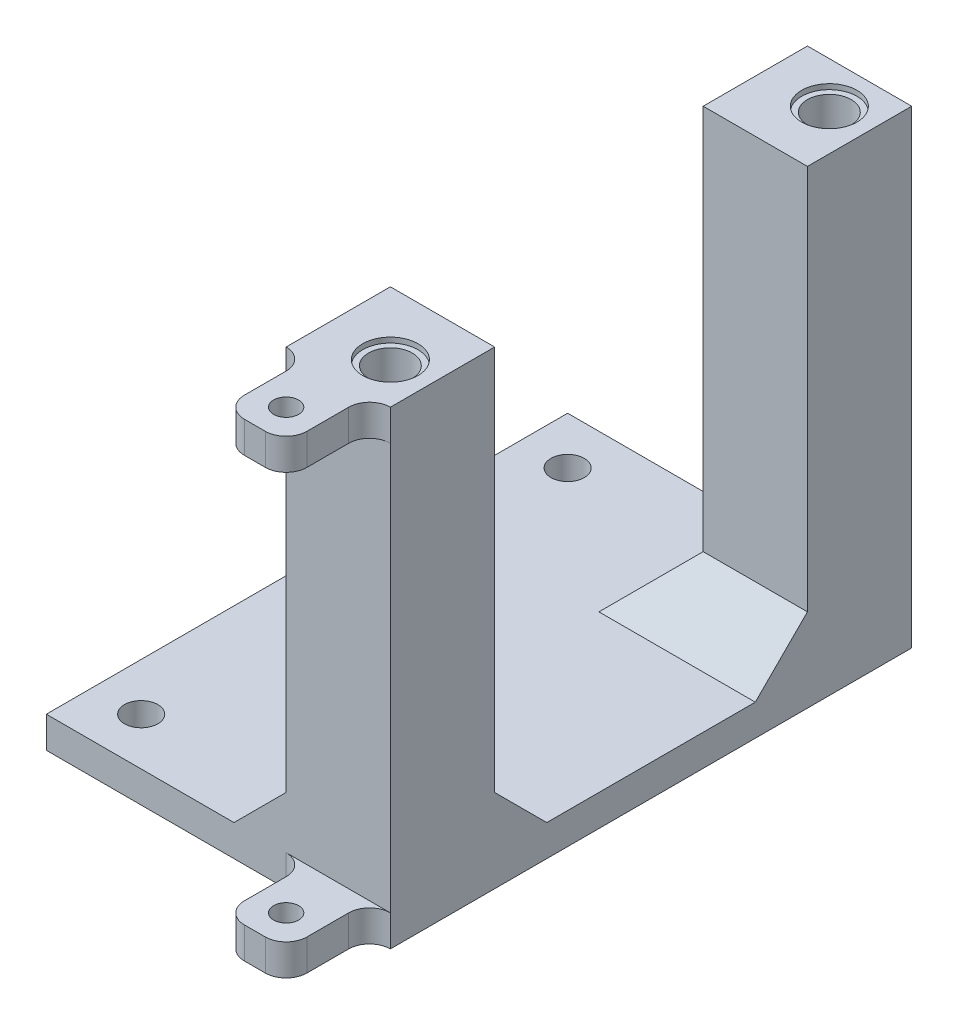
SolidWorks part; units mm, degrees
ref_plane "Front Plane" through (0, 0, 0) normal (0, 0, 1) x (1, 0, 0)
ref_plane "Top Plane" through (0, 0, 0) normal (0, 1, 0) x (1, 0, 0)
ref_plane "Right Plane" through (0, 0, 0) normal (1, 0, 0) x (0, 0, -1)
sketch "Sketch1" plane through (0, 0, 0) normal (0, 1, 0) x (1, 0, 0)
  line L1 (-6.5124, 9.686) -> (1.4876, 9.686)
  line L2 (-6.5124, 9.686) -> (-6.5124, -40.314)
  line L3 (-6.5124, -40.314) -> (1.4876, -40.314)
  line L4 (1.4876, 9.686) -> (1.4876, -40.314)
  line L5 (1.4876, 9.686) -> (26.4876, 9.686)
  line L6 (1.4876, 9.686) -> (1.4876, -40.314)
  line L7 (1.4876, -40.314) -> (26.4876, -40.314)
  line L8 (26.4876, 9.686) -> (26.4876, -40.314)
  circle A0 centre (-1.9624, -35.764) radius 1.6
  circle A1 centre (-1.9624, 5.136) radius 1.6
  dimension "D4" = 3.2
  dimension "D5" = 3.2
  dimension "D6" = 4.55
  dimension "D7" = 4.55
  dimension "D8" = 4.55
  dimension "D9" = 4.55
  dimension "D1" = 8
  dimension "D2" = 50
  dimension "D3" = 25
extrude "Boss-Extrude1" add sketch "Sketch1" along normal blind 3 contours A1 | A0 | L5 L8 L7 L3 L2 L1
sketch "Sketch2" plane through (0, 3, 0) normal (0, 1, 0) x (1, 0, 0)
  line L1 (26.4876, -40.314) -> (16.4876, -40.314)
  line L2 (26.4876, -40.314) -> (26.4876, -30.314)
  line L3 (26.4876, -30.314) -> (16.4876, -30.314)
  line L4 (16.4876, -40.314) -> (16.4876, -30.314)
  line L5 (26.4876, 9.686) -> (16.4876, 9.686)
  line L6 (26.4876, 9.686) -> (26.4876, -0.314)
  line L7 (26.4876, -0.314) -> (16.4876, -0.314)
  line L8 (16.4876, 9.686) -> (16.4876, -0.314)
  dimension "D1" = 10
  dimension "D2" = 10
  dimension "D3" = 10
  dimension "D4" = 10
extrude "Boss-Extrude2" add sketch "Sketch2" along normal blind 42
chamfer "Chamfer1" distance 5 angle 45 4 edges at (16.4876, 3, -4.686) (21.4876, 3, 0.314) (16.4876, 3, 35.314) (21.4876, 3, 30.314)
ref_plane "Plane1" through (0, 45, 0) normal (0, 1, 0) x (1, 0, 0)
sketch "Sketch3" plane through (0, 45, 0) normal (0, 1, 0) x (1, 0, 0)
  line L0 (26.4876, -40.314) -> (26.4876, -30.314) construction
  line L1 (16.4876, -40.314) -> (26.4876, -40.314) construction
  line L2 (26.4876, -0.314) -> (26.4876, 9.686) construction
  line L3 (26.4876, 9.686) -> (16.4876, 9.686) construction
  circle A0 centre (22.5376, -36.364) radius 2.1
  circle A1 centre (22.5376, 5.736) radius 2.1
  dimension "D1" = 4.2
  dimension "D3" = 3.95
  dimension "D4" = 4.2
  dimension "D6" = 3.95
  dimension "D2" = 3.95
  dimension "D5" = 3.95
extrude "Cut-Extrude1" cut sketch "Sketch3" against normal blind 52
sketch "Sketch4" plane through (0, 45, 0) normal (0, 1, 0) x (1, 0, 0)
  circle A0 centre (22.5376, -36.364) radius 2.65
  circle A1 centre (22.5376, 5.736) radius 2.65
  dimension "D1" = 5.3
  dimension "D2" = 5.3
extrude "Cut-Extrude2" cut sketch "Sketch4" against normal blind 0.5
ref_plane "Plane2" through (0, 22.5, 0) normal (0, -1, 0) x (-1, 0, 0)
mirror "Mirror1" about plane through (0, 22.5, 0) normal (0, -1, 0) of "Cut-Extrude2"
sketch "Sketch5" plane through (0, 0, -9.686) normal (0, 0, -1) x (-1, 0, 0)
  line L0 (-22.4876, 36.5) -> (-17.9876, 36.5) construction
  line L1 (-18.2876, 36.2) -> (-22.2399, 36.2)
  line L2 (-18.2876, 36.2) -> (-18.2876, 31.6868)
  line L3 (-18.2876, 31.6868) -> (-22.2399, 31.6868)
  line L4 (-22.2399, 36.2) -> (-22.2399, 31.6868)
  line L5 (-17.9876, 32.25) -> (-17.9876, 37) construction
  dimension "D1" = 0.3
  dimension "D2" = 0.3
sketch "Sketch11" plane through (0, 0, 40.314) normal (0, 0, 1) x (1, 0, 0)
  line L0 (16.4876, 45) -> (26.4876, 45) construction
  line L1 (18.4876, 45) -> (24.4876, 45)
  line L2 (18.4876, 45) -> (18.4876, 42)
  line L3 (18.4876, 42) -> (24.4876, 42)
  line L4 (24.4876, 45) -> (24.4876, 42)
  line L5 (-6.5124, 0) -> (26.4876, 0) construction
  line L6 (18.4876, 0) -> (24.4876, 0)
  line L7 (18.4876, 0) -> (18.4876, 3)
  line L8 (18.4876, 3) -> (24.4876, 3)
  line L9 (24.4876, 0) -> (24.4876, 3)
  line L10 (21.4876, 8) -> (21.4876, 0) construction
  line L11 (21.4876, 8) -> (21.4876, 45) construction
  line L13 (-6.5124, 3) -> (11.4876, 3) construction
  line L14 (16.4876, 8) -> (26.4876, 8) construction
  line L15 (26.4876, 8) -> (39.3241, 4.4212) construction
  line L16 (39.3241, 4.4212) -> (39.5028, 4.4212) construction
  dimension "D1" = 3
  dimension "D2" = 3
  dimension "D3" = 3
  dimension "D4" = 3
  dimension "D5" = 3
extrude "Boss-Extrude7" add sketch "Sketch11" along normal blind 8
sketch "Sketch12" plane through (0, 0, 0) normal (0, -1, 0) x (1, 0, 0)
  line L0 (24.4876, 48.314) -> (24.4876, 40.314) construction
  line L1 (18.4876, 48.314) -> (24.4876, 48.314) construction
  line L2 (18.4876, 48.314) -> (18.4876, 42.314) construction
  line L3 (18.4876, 42.314) -> (24.4876, 42.314) construction
  line L4 (24.4876, 48.314) -> (24.4876, 42.314) construction
  line L5 (18.4876, 48.314) -> (24.4876, 42.314) construction
  line L6 (18.4876, 42.314) -> (24.4876, 48.314) construction
  circle A0 centre (21.4876, 45.314) radius 1.2
  point P6 (0, 0)
  point P494 (21.4876, 45.314)
  dimension "D1" = 2.4
  dimension "D2" = 6
extrude "Cut-Extrude5" cut sketch "Sketch12" against normal through all
fillet "Fillet1" radius 2 8 edges at (18.4876, 43.5, 40.314) (18.4876, 43.5, 48.314) (24.4876, 43.5, 48.314) (24.4876, 43.5, 40.314) (24.4876, 1.5, 48.314) (18.4876, 1.5, 48.314) (18.4876, 1.5, 40.314) (24.4876, 1.5, 40.314)
